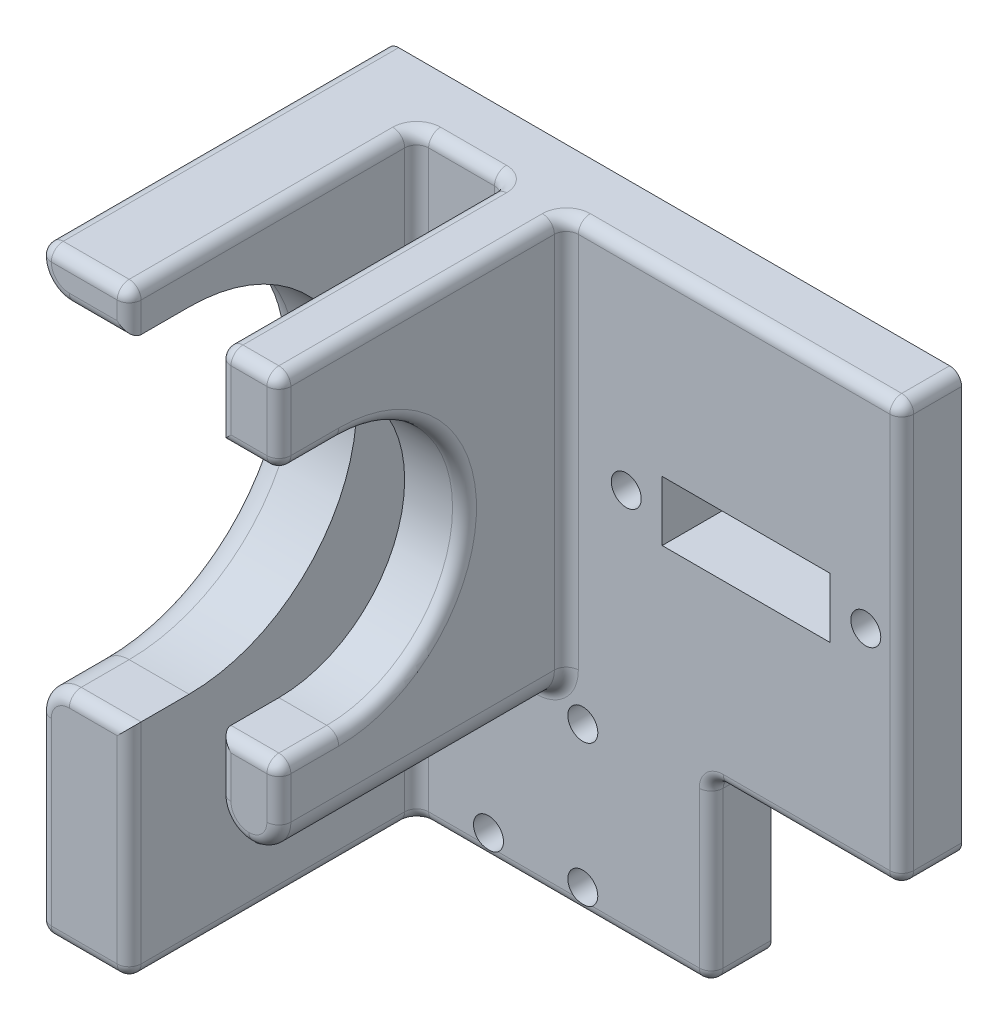
SolidWorks part; units mm, degrees
ref_plane "Front Plane" through (0, 0, 0) normal (0, 0, 1) x (1, 0, 0)
ref_plane "Top Plane" through (0, 0, 0) normal (0, 1, 0) x (1, 0, 0)
ref_plane "Right Plane" through (0, 0, 0) normal (1, 0, 0) x (0, 0, -1)
sketch "Sketch1" plane through (0, 0, 0) normal (0, 0, 1) x (1, 0, 0)
  line L1 (0, 0) -> (60.96, 0)
  line L2 (0, 0) -> (0, 44.45)
  line L3 (0, 44.45) -> (60.96, 44.45)
  line L4 (60.96, 0) -> (60.96, 44.45)
  dimension "D1" = 44.45
  dimension "D2" = 60.96
extrude "Boss-Extrude1" add sketch "Sketch1" along normal blind 6.35
sketch "Sketch2" plane through (0, 0, 6.35) normal (0, 0, 1) x (1, 0, 0)
  line L0 (60.96, 44.45) -> (0, 44.45) construction
  line L1 (0, 0) -> (9.525, 0)
  line L2 (0, 0) -> (0, 44.45)
  line L3 (0, 44.45) -> (9.525, 44.45)
  line L4 (9.525, 0) -> (9.525, 44.45)
  line L5 (0, 0) -> (60.96, 0) construction
  line L6 (60.96, 0) -> (60.96, 44.45) construction
  line L7 (25.4, 44.45) -> (19.05, 44.45)
  line L8 (25.4, 44.45) -> (25.4, 0)
  line L9 (25.4, 0) -> (19.05, 0)
  line L10 (19.05, 44.45) -> (19.05, 0)
  dimension "D1" = 35.56
  dimension "D2" = 6.35
  dimension "D3" = 9.525
extrude "Boss-Extrude2" add sketch "Sketch2" along normal blind 44.45
sketch "Sketch3" plane through (0, 0, 0) normal (-1, 0, 0) x (0, 0, 1)
  line L0 (50.8, 44.45) -> (0, 44.45) construction
  line L2 (30.48, 35.56) -> (36.83, 35.56)
  line L3 (50.8, 44.45) -> (50.8, 0)
  line L4 (36.83, 8.89) -> (30.48, 8.89)
  line L5 (6.35, 0) -> (6.35, 44.45) construction
  line L6 (36.83, 35.56) -> (36.83, 44.45)
  line L7 (36.83, 44.45) -> (50.8, 44.45)
  line L8 (36.83, 8.89) -> (36.83, 0)
  line L9 (50.8, 0) -> (0, 0) construction
  line L10 (36.83, 0) -> (50.8, 0)
  arc A0 (30.48, 35.56) -> (30.48, 8.89) centre (30.48, 22.225) ccw
  dimension "D2" = 26.67
  dimension "D4" = 6.35
  dimension "D1" = 22.225
  dimension "D3" = 24.13
extrude "Cut-Extrude1" cut sketch "Sketch3" against normal through all
sketch "Sketch4" plane through (0, 0, 6.35) normal (0, 0, 1) x (1, 0, 0)
  line L0 (25.4, 0) -> (60.96, 0) construction
  line L1 (60.96, 0) -> (60.96, 44.45) construction
  circle A0 centre (57.15, 22.225) radius 1.5875
  circle A1 centre (31.75, 22.225) radius 1.5875
  dimension "D1" = 3.175
  dimension "D2" = 22.225
  dimension "D3" = 3.81
  dimension "D4" = 25.4
extrude "Cut-Extrude2" cut sketch "Sketch4" against normal blind 44.45
sketch "Sketch6" plane through (0, 0, 6.35) normal (0, 0, 1) x (1, 0, 0)
  line L0 (31.75, 22.225) -> (57.15, 22.225) construction
  line L1 (53.34, 25.4) -> (35.56, 25.4)
  line L2 (53.34, 25.4) -> (53.34, 19.05)
  line L3 (53.34, 19.05) -> (35.56, 19.05)
  line L4 (35.56, 25.4) -> (35.56, 19.05)
  line L5 (35.56, 19.05) -> (53.34, 25.4) construction
  point P8 (44.45, 22.225)
  dimension "D1" = 17.78
  dimension "D2" = 6.35
extrude "Cut-Extrude3" cut sketch "Sketch6" against normal through all
sketch "Sketch7" plane through (0, 0, 0) normal (0, -1, 0) x (1, 0, 0)
  line L0 (0, 0) -> (60.96, 0) construction
  line L1 (0, 36.83) -> (9.525, 36.83)
  line L2 (0, 36.83) -> (0, 0)
  line L3 (0, 0) -> (9.525, 0)
  line L4 (9.525, 36.83) -> (9.525, 0)
  line L5 (9.525, 36.83) -> (9.525, 6.35) construction
extrude "Boss-Extrude3" add sketch "Sketch7" along normal blind 19.05
sketch "Sketch8" plane through (0, 0, 0) normal (-1, 0, 0) x (0, 0, 1)
  circle A0 centre (22.1996, -11.6586) radius 3.048
  arc A1 (30.48, 35.56) -> (30.48, 8.89) centre (30.48, 22.225) ccw construction
  point P2 (17.145, 22.225)
  dimension "D3" = 6.096
  dimension "D1" = 33.8836
  dimension "D2" = 8.2804
extrude "Cut-Extrude4" cut sketch "Sketch8" against normal blind 3.175
sketch "Sketch9" plane through (0, 0, 0) normal (-1, 0, 0) x (0, 0, 1)
  circle A0 centre (22.1996, -11.6586) radius 1.5875
  dimension "D1" = 3.175
extrude "Cut-Extrude5" cut sketch "Sketch9" against normal through all
sketch "Sketch10" plane through (0, 0, 0) normal (-1, 0, 0) x (0, 0, 1)
  line L0 (30.48, 4.445) -> (36.83, 4.445)
  line L1 (36.83, 8.89) -> (36.83, -19.05) construction
  line L2 (36.83, 4.445) -> (36.83, 40.005)
  line L3 (36.83, 44.45) -> (36.83, 35.56) construction
  line L4 (36.83, 40.005) -> (30.48, 40.005)
  arc A0 (30.48, 40.005) -> (30.48, 4.445) centre (30.48, 22.225) ccw
  arc A1 (30.48, 35.56) -> (30.48, 8.89) centre (30.48, 22.225) ccw construction
  dimension "D1" = 35.56
extrude "Cut-Extrude6" cut sketch "Sketch10" against normal up to next
sketch "Sketch12" plane through (0, 0, 0) normal (0, -1, 0) x (1, 0, 0)
  line L0 (9.525, 0) -> (60.96, 0) construction
  line L1 (9.525, 6.35) -> (40.7619, 6.35)
  line L2 (9.525, 6.35) -> (9.525, 0)
  line L3 (9.525, 0) -> (40.7619, 0)
  line L4 (40.7619, 6.35) -> (40.7619, 0)
extrude "Boss-Extrude4" add sketch "Sketch12" along normal up to surface (19.05 mm away) up to face at (4.7625, -19.05, 18.415)
fillet "Fillet1" radius 3.175 3 edges at (0, 40.005, 33.655) (0, 22.225, 12.7) (0, 4.445, 33.655)
sketch "Sketch11" plane through (0, 0, 0) normal (0, 0, -1) x (-1, 0, 0)
  line L1 (-27.145, -16.55) -> (-17.145, -16.55) construction
  line L3 (0, -19.05) -> (-40.7619, -19.05) construction
  line L4 (-9.525, -19.05) -> (-9.525, 44.45) construction
  circle A0 centre (-27.145, -16.55) radius 1.5875
  circle A1 centre (-17.145, -16.55) radius 1.5875
  circle A2 centre (-17.145, -1.55) radius 1.5875
  circle A3 centre (-27.145, -1.55) radius 1.5875
  point P8 (-22.145, -16.55)
  dimension "D1" = 3.175
  dimension "D2" = 10
  dimension "D3" = 15
  dimension "D4" = 7.62
  dimension "D5" = 2.5
extrude "Cut-Extrude7" cut sketch "Sketch11" against normal through all
fillet "Fillet3" radius 3.175 2 edges at (19.05, 0, 21.59) (25.4, 0, 21.59)
fillet "Fillet4" radius 1.27 42 edges at (19.05, 23.8125, 6.35) (19.9799, 0.9299, 6.35) (24.4701, 0.9299, 6.35) (19.05, 6.0325, 36.83) (19.9799, 0.9299, 36.83) (24.4701, 0.9299, 36.83) (25.4, 35.56, 33.655) (25.4, 8.89, 33.655) (6.35, 40.005, 36.83) (0.9299, 40.9349, 36.83) (6.35, 4.445, 36.83) (0.9299, 3.5151, 36.83) (22.225, 8.89, 36.83) (40.7619, -19.05, 3.175) (40.7619, 0, 3.175) (60.96, 0, 3.175) (60.96, 44.45, 3.175) (25.4, 23.8125, 6.35) (9.525, 42.2275, 36.83) (9.525, -7.3025, 36.83) (25.4, 6.0325, 36.83) (25.4, 22.225, 17.145) (19.05, 40.005, 36.83) (22.225, 35.56, 36.83) (25.4, 40.005, 36.83) (22.225, 44.45, 36.83) (19.05, 44.45, 21.59) (25.4, 44.45, 21.59) (0, 44.45, 18.415) (4.7625, 44.45, 36.83) (0, -8.89, 36.83) (0, -19.05, 18.415) (4.7625, -19.05, 36.83) (9.525, -19.05, 21.59) (25.1435, -19.05, 6.35) (60.96, 22.225, 6.35) (40.7619, -9.525, 6.35)
equation "\"2.4n\"=2.275"
